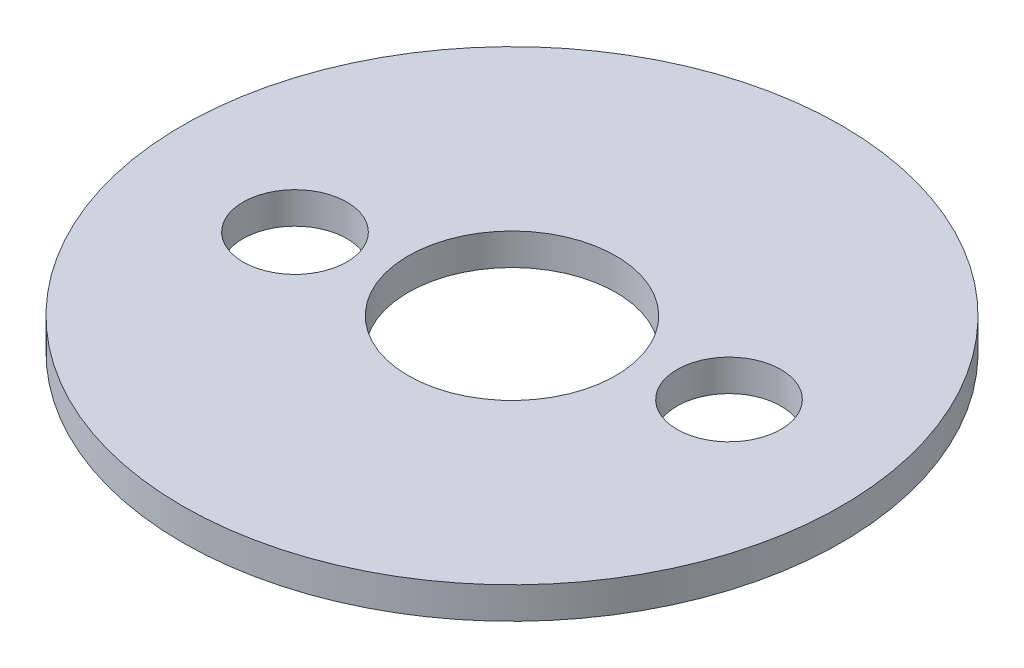
SolidWorks part; units mm, degrees
material "Alum Plate"
ref_plane "Front Plane" through (0, 0, 0) normal (0, 0, 1) x (1, 0, 0)
ref_plane "Top Plane" through (0, 0, 0) normal (0, 1, 0) x (1, 0, 0)
ref_plane "Right Plane" through (0, 0, 0) normal (1, 0, 0) x (0, 0, -1)
other "Bounding Box"
ref_plane "Default Plane" through (-8.9266, -12.7485, 0) normal (-0.1736, 0.9848, 0) x (0.9848, 0.1736, 0)
sketch "Sketch1" plane through (0, 0, 0) normal (0, 1, 0) x (1, 0, 0)
  line L0 (0, -7.8245) -> (0, 0) construction
  circle A0 centre (0, 0) radius 2.5
  arc B0 (-1.8508, -6.777) -> (-1.6633, -7.0715) centre (-1.6061, -6.8282) ccw
  arc B1 (-1.6633, -7.0715) -> (-1.1695, -7.1697) centre (0, 0) ccw
  arc B2 (-1.1695, -7.1697) -> (-0.8836, -6.9694) centre (-1.1292, -6.923) ccw
  arc B3 (-0.7739, -6.6229) -> (-0.8836, -6.9694) centre (0.61, -7.2516) ccw
  arc B4 (0.7739, -6.6229) -> (-0.7739, -6.6229) centre (0, -6.9745) ccw
  arc B5 (0.8836, -6.9694) -> (0.7739, -6.6229) centre (-0.61, -7.2516) ccw
  arc B6 (0.8836, -6.9694) -> (1.1695, -7.1697) centre (1.1292, -6.923) ccw
  arc B7 (1.1695, -7.1697) -> (1.6633, -7.0715) centre (0, 0) ccw
  arc B8 (1.6633, -7.0715) -> (1.8508, -6.777) centre (1.6061, -6.8282) ccw
  arc B9 (1.8195, -6.4149) -> (1.8508, -6.777) centre (3.3386, -6.4662) ccw
  arc B10 (3.2495, -5.8226) -> (1.8195, -6.4149) centre (2.669, -6.4436) ccw
  arc B11 (3.4834, -6.1008) -> (3.2495, -5.8226) centre (2.2115, -6.9331) ccw
  arc B12 (3.4834, -6.1008) -> (3.8242, -6.1764) centre (3.6926, -5.9639) ccw
  arc B13 (3.8242, -6.1764) -> (4.2428, -5.8967) centre (0, 0) ccw
  arc B14 (4.2428, -5.8967) -> (4.3033, -5.5529) centre (4.0968, -5.6938) ccw
  arc B15 (4.1359, -5.2303) -> (4.3033, -5.5529) centre (5.559, -4.6963) ccw
  arc B16 (5.2303, -4.1359) -> (4.1359, -5.2303) centre (4.9317, -4.9317) ccw
  arc B17 (5.5529, -4.3033) -> (5.2303, -4.1359) centre (4.6963, -5.559) ccw
  arc B18 (5.5529, -4.3033) -> (5.8967, -4.2428) centre (5.6938, -4.0968) ccw
  arc B19 (5.8967, -4.2428) -> (6.1764, -3.8242) centre (0, 0) ccw
  arc B20 (6.1764, -3.8242) -> (6.1008, -3.4834) centre (5.9639, -3.6926) ccw
  arc B21 (5.8226, -3.2495) -> (6.1008, -3.4834) centre (6.9331, -2.2115) ccw
  arc B22 (6.4149, -1.8195) -> (5.8226, -3.2495) centre (6.4436, -2.669) ccw
  arc B23 (6.777, -1.8508) -> (6.4149, -1.8195) centre (6.4662, -3.3386) ccw
  arc B24 (6.777, -1.8508) -> (7.0715, -1.6633) centre (6.8282, -1.6061) ccw
  arc B25 (7.0715, -1.6633) -> (7.1697, -1.1695) centre (0, 0) ccw
  arc B26 (7.1697, -1.1695) -> (6.9694, -0.8836) centre (6.923, -1.1292) ccw
  arc B27 (6.6229, -0.7739) -> (6.9694, -0.8836) centre (7.2516, 0.61) ccw
  arc B28 (6.6229, 0.7739) -> (6.6229, -0.7739) centre (6.9745, 0) ccw
  arc B29 (6.9694, 0.8836) -> (6.6229, 0.7739) centre (7.2516, -0.61) ccw
  arc B30 (6.9694, 0.8836) -> (7.1697, 1.1695) centre (6.923, 1.1292) ccw
  arc B31 (7.1697, 1.1695) -> (7.0715, 1.6633) centre (0, 0) ccw
  arc B32 (7.0715, 1.6633) -> (6.777, 1.8508) centre (6.8282, 1.6061) ccw
  arc B33 (6.4149, 1.8195) -> (6.777, 1.8508) centre (6.4662, 3.3386) ccw
  arc B34 (5.8226, 3.2495) -> (6.4149, 1.8195) centre (6.4436, 2.669) ccw
  arc B35 (6.1008, 3.4834) -> (5.8226, 3.2495) centre (6.9331, 2.2115) ccw
  arc B36 (6.1008, 3.4834) -> (6.1764, 3.8242) centre (5.9639, 3.6926) ccw
  arc B37 (6.1764, 3.8242) -> (5.8967, 4.2428) centre (0, 0) ccw
  arc B38 (5.8967, 4.2428) -> (5.5529, 4.3033) centre (5.6938, 4.0968) ccw
  arc B39 (5.2303, 4.1359) -> (5.5529, 4.3033) centre (4.6963, 5.559) ccw
  arc B40 (4.1359, 5.2303) -> (5.2303, 4.1359) centre (4.9317, 4.9317) ccw
  arc B41 (4.3033, 5.5529) -> (4.1359, 5.2303) centre (5.559, 4.6963) ccw
  arc B42 (4.3033, 5.5529) -> (4.2428, 5.8967) centre (4.0968, 5.6938) ccw
  arc B43 (4.2428, 5.8967) -> (3.8242, 6.1764) centre (0, 0) ccw
  arc B44 (3.8242, 6.1764) -> (3.4834, 6.1008) centre (3.6926, 5.9639) ccw
  arc B45 (3.2495, 5.8226) -> (3.4834, 6.1008) centre (2.2115, 6.9331) ccw
  arc B46 (1.8195, 6.4149) -> (3.2495, 5.8226) centre (2.669, 6.4436) ccw
  arc B47 (1.8508, 6.777) -> (1.8195, 6.4149) centre (3.3386, 6.4662) ccw
  arc B48 (1.8508, 6.777) -> (1.6633, 7.0715) centre (1.6061, 6.8282) ccw
  arc B49 (1.6633, 7.0715) -> (1.1695, 7.1697) centre (0, 0) ccw
  arc B50 (1.1695, 7.1697) -> (0.8836, 6.9694) centre (1.1292, 6.923) ccw
  arc B51 (0.7739, 6.6229) -> (0.8836, 6.9694) centre (-0.61, 7.2516) ccw
  arc B52 (-0.7739, 6.6229) -> (0.7739, 6.6229) centre (0, 6.9745) ccw
  arc B53 (-0.8836, 6.9694) -> (-0.7739, 6.6229) centre (0.61, 7.2516) ccw
  arc B54 (-0.8836, 6.9694) -> (-1.1695, 7.1697) centre (-1.1292, 6.923) ccw
  arc B55 (-1.1695, 7.1697) -> (-1.6633, 7.0715) centre (0, 0) ccw
  arc B56 (-1.6633, 7.0715) -> (-1.8508, 6.777) centre (-1.6061, 6.8282) ccw
  arc B57 (-1.8195, 6.4149) -> (-1.8508, 6.777) centre (-3.3386, 6.4662) ccw
  arc B58 (-3.2495, 5.8226) -> (-1.8195, 6.4149) centre (-2.669, 6.4436) ccw
  arc B59 (-3.4834, 6.1008) -> (-3.2495, 5.8226) centre (-2.2115, 6.9331) ccw
  arc B60 (-3.4834, 6.1008) -> (-3.8242, 6.1764) centre (-3.6926, 5.9639) ccw
  arc B61 (-3.8242, 6.1764) -> (-4.2428, 5.8967) centre (0, 0) ccw
  arc B62 (-4.2428, 5.8967) -> (-4.3033, 5.5529) centre (-4.0968, 5.6938) ccw
  arc B63 (-4.1359, 5.2303) -> (-4.3033, 5.5529) centre (-5.559, 4.6963) ccw
  arc B64 (-5.2303, 4.1359) -> (-4.1359, 5.2303) centre (-4.9317, 4.9317) ccw
  arc B65 (-5.5529, 4.3033) -> (-5.2303, 4.1359) centre (-4.6963, 5.559) ccw
  arc B66 (-5.5529, 4.3033) -> (-5.8967, 4.2428) centre (-5.6938, 4.0968) ccw
  arc B67 (-5.8967, 4.2428) -> (-6.1764, 3.8242) centre (0, 0) ccw
  arc B68 (-6.1764, 3.8242) -> (-6.1008, 3.4834) centre (-5.9639, 3.6926) ccw
  arc B69 (-5.8226, 3.2495) -> (-6.1008, 3.4834) centre (-6.9331, 2.2115) ccw
  arc B70 (-6.4149, 1.8195) -> (-5.8226, 3.2495) centre (-6.4436, 2.669) ccw
  arc B71 (-6.777, 1.8508) -> (-6.4149, 1.8195) centre (-6.4662, 3.3386) ccw
  arc B72 (-6.777, 1.8508) -> (-7.0715, 1.6633) centre (-6.8282, 1.6061) ccw
  arc B73 (-7.0715, 1.6633) -> (-7.1697, 1.1695) centre (0, 0) ccw
  arc B74 (-7.1697, 1.1695) -> (-6.9694, 0.8836) centre (-6.923, 1.1292) ccw
  arc B75 (-6.6229, 0.7739) -> (-6.9694, 0.8836) centre (-7.2516, -0.61) ccw
  arc B76 (-6.6229, -0.7739) -> (-6.6229, 0.7739) centre (-6.9745, 0) ccw
  arc B77 (-6.9694, -0.8836) -> (-6.6229, -0.7739) centre (-7.2516, 0.61) ccw
  arc B78 (-6.9694, -0.8836) -> (-7.1697, -1.1695) centre (-6.923, -1.1292) ccw
  arc B79 (-7.1697, -1.1695) -> (-7.0715, -1.6633) centre (0, 0) ccw
  arc B80 (-7.0715, -1.6633) -> (-6.777, -1.8508) centre (-6.8282, -1.6061) ccw
  arc B81 (-6.4149, -1.8195) -> (-6.777, -1.8508) centre (-6.4662, -3.3386) ccw
  arc B82 (-5.8226, -3.2495) -> (-6.4149, -1.8195) centre (-6.4436, -2.669) ccw
  arc B83 (-6.1008, -3.4834) -> (-5.8226, -3.2495) centre (-6.9331, -2.2115) ccw
  arc B84 (-6.1008, -3.4834) -> (-6.1764, -3.8242) centre (-5.9639, -3.6926) ccw
  arc B85 (-6.1764, -3.8242) -> (-5.8967, -4.2428) centre (0, 0) ccw
  arc B86 (-5.8967, -4.2428) -> (-5.5529, -4.3033) centre (-5.6938, -4.0968) ccw
  arc B87 (-5.2303, -4.1359) -> (-5.5529, -4.3033) centre (-4.6963, -5.559) ccw
  arc B88 (-4.1359, -5.2303) -> (-5.2303, -4.1359) centre (-4.9317, -4.9317) ccw
  arc B89 (-4.3033, -5.5529) -> (-4.1359, -5.2303) centre (-5.559, -4.6963) ccw
  arc B90 (-4.3033, -5.5529) -> (-4.2428, -5.8967) centre (-4.0968, -5.6938) ccw
  arc B91 (-4.2428, -5.8967) -> (-3.8242, -6.1764) centre (0, 0) ccw
  arc B92 (-3.8242, -6.1764) -> (-3.4834, -6.1008) centre (-3.6926, -5.9639) ccw
  arc B93 (-3.2495, -5.8226) -> (-3.4834, -6.1008) centre (-2.2115, -6.9331) ccw
  arc B94 (-1.8195, -6.4149) -> (-3.2495, -5.8226) centre (-2.669, -6.4436) ccw
  arc B95 (-1.8508, -6.777) -> (-1.8195, -6.4149) centre (-3.3386, -6.4662) ccw
  dimension "D1" = 5
sketch_block_instance "Block-GT2 16 Tooth Profile-1"
sketch_block "Block-GT2 16 Tooth Profile"
extrude "Boss-Extrude1" add sketch "Sketch1" along normal mid plane 9.525
sketch "Sketch2" plane through (0, -4.7625, 0) normal (0, -1, 0) x (1, 0, 0)
  circle A0 centre (0, 0) radius 7.9375
  circle A1 centre (0, 0) radius 2.5 construction
  circle A2 centre (0, 0) radius 2.5
  dimension "D1" = 15.875
extrude "Boss-Extrude2" add sketch "Sketch2" along normal blind 0.762 separate body
sketch "Sketch4" plane through (0, -4.7625, 0) normal (0, -1, 0) x (1, 0, 0)
  line L0 (-4.3596, 0.8672) -> (0, 0) construction
  line L1 (0, 0) -> (4.3596, -0.8672) construction
  line L2 (-7.1249, 1.4172) -> (-4.3596, 0.8672) construction
  circle A0 centre (-4.3596, 0.8672) radius 1
  circle A1 centre (4.3596, -0.8672) radius 1
  arc A2 (-7.0715, 1.6633) -> (-7.1697, 1.1695) centre (0, 0) ccw construction
  dimension "D1" = 2
  dimension "D2" = 4.445
extrude "Cut-Extrude2" cut sketch "Sketch4" against normal through all
sketch "Sketch5" plane through (0, -4.7625, 0) normal (0, 1, 0) x (1, 0, 0)
  circle A0 centre (-4.3596, -0.8672) radius 1.25
  circle A1 centre (4.3596, 0.8672) radius 1.25
  dimension "D1" = 2.5
extrude "Cut-Extrude3" cut sketch "Sketch5" against normal through all
delete or keep bodies "Body-Delete/Keep 1" [suppressed] type delete bodies bodies 111
delete or keep bodies "Body-Delete/Keep 2" type delete bodies bodies 108
